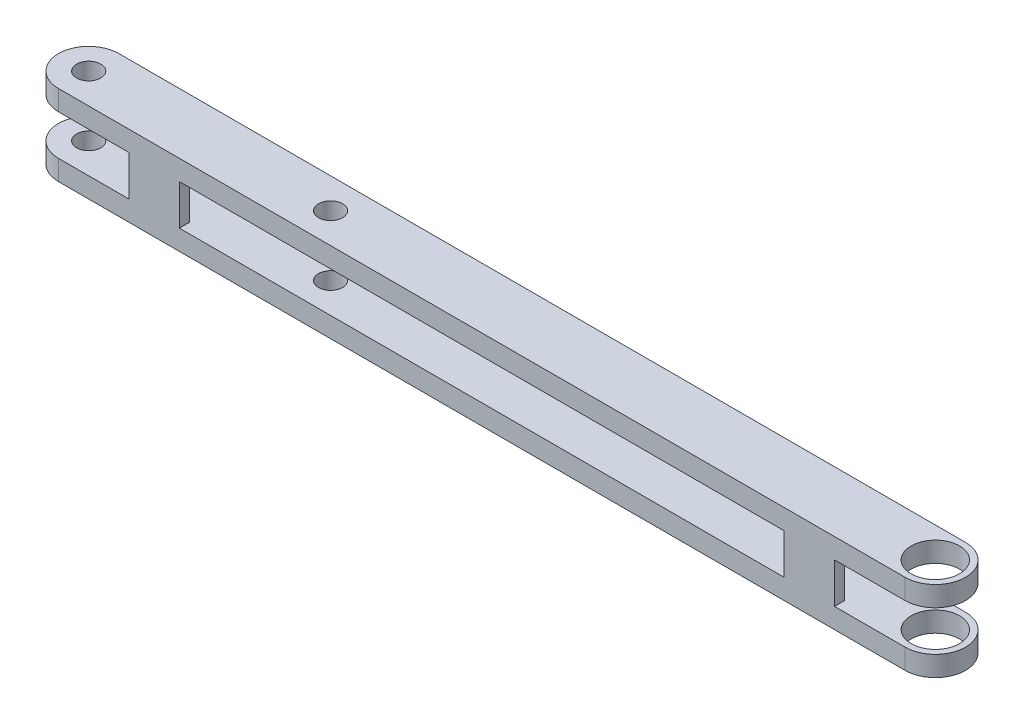
SolidWorks part; units mm, degrees
ref_plane "前视基准面" through (0, 0, 0) normal (0, 0, 1) x (1, 0, 0)
ref_plane "上视基准面" through (0, 0, 0) normal (0, 1, 0) x (1, 0, 0)
ref_plane "右视基准面" through (0, 0, 0) normal (1, 0, 0) x (0, 0, -1)
sketch "草图1" plane through (0, 0, 0) normal (0, 1, 0) x (1, 0, 0)
  line L0 (-105, 0) -> (105, 0) construction
  line L1 (-105, 7.5) -> (105, 7.5)
  line L2 (-105, -7.5) -> (105, -7.5)
  arc A0 (-105, 7.5) -> (-105, -7.5) centre (-105, 0) ccw
  arc A1 (105, -7.5) -> (105, 7.5) centre (105, 0) ccw
  point P3 (0, 0)
  dimension "D1" = 210
  dimension "D2" = 15
extrude "凸台-拉伸1" add sketch "草图1" along normal blind 20
sketch "草图2" plane through (0, 0, -7.5) normal (0, 0, -1) x (-1, 0, 0)
  line L0 (0, 0) -> (0, 10) construction
  line L1 (75, 5) -> (-75, 5)
  line L2 (75, 5) -> (75, 15)
  line L3 (75, 15) -> (-75, 15)
  line L4 (-75, 5) -> (-75, 15)
  line L5 (75, 5) -> (-75, 15) construction
  line L6 (75, 15) -> (-75, 5) construction
  line L7 (-105, 0) -> (105, 0) construction
  point P0 (0, 10)
  dimension "D1" = 10
  dimension "D2" = 10
  dimension "D3" = 150
extrude "切除-拉伸3" cut sketch "草图2" against normal through all
sketch "草图3" plane through (0, 0, -7.5) normal (0, 0, -1) x (-1, 0, 0)
  line L0 (-75, 5) -> (75, 5) construction
  line L1 (112.5, 15) -> (87.5, 15)
  line L2 (112.5, 15) -> (112.5, 5)
  line L3 (112.5, 5) -> (87.5, 5)
  line L4 (87.5, 15) -> (87.5, 5)
  line L5 (75, 15) -> (-75, 15) construction
  line L6 (112.5, 0) -> (112.5, 20) construction
  line L7 (0, 0) -> (0, 43.872) construction
  line L8 (-105, 0) -> (105, 0) construction
  line L9 (-87.5, 15) -> (-87.5, 5)
  line L10 (-112.5, 5) -> (-87.5, 5)
  line L11 (-112.5, 15) -> (-112.5, 5)
  line L12 (-112.5, 15) -> (-87.5, 15)
  dimension "D1" = 25
extrude "切除-拉伸4" cut sketch "草图3" against normal through all
sketch "草图4" plane through (-87.5, 0, 0) normal (-1, 0, 0) x (0, 0, 1)
  line L0 (7.5, 5) -> (-7.5, 5) construction
  line L1 (5, 15) -> (-5, 15)
  line L2 (5, 15) -> (5, 5)
  line L3 (5, 5) -> (-5, 5)
  line L4 (-5, 15) -> (-5, 5)
  line L5 (5, 15) -> (-5, 5) construction
  line L6 (5, 5) -> (-5, 15) construction
  line L7 (0, 0) -> (0, 10) construction
  line L8 (7.5, 15) -> (-7.5, 15) construction
  point P0 (0, 10)
  dimension "D1" = 10
extrude "切除-拉伸5" cut sketch "草图4" against normal through all
sketch "草图5" plane through (0, 20, 0) normal (0, 1, 0) x (1, 0, 0)
  line L0 (-105, 0) -> (0, 0) construction
  line L1 (0, 0) -> (105, 0) construction
  circle A0 centre (-105, 0) radius 3
  circle A1 centre (105, 0) radius 6
  dimension "D1" = 6
  dimension "D2" = 12
  dimension "D3" = 105
  dimension "D4" = 105
extrude "切除-拉伸6" cut sketch "草图5" against normal through all
sketch "草图6" plane through (0, 20, 0) normal (0, 1, 0) x (1, 0, 0)
  line L0 (-45, 0) -> (0, 0) construction
  circle A0 centre (-45, 0) radius 3
  circle A1 centre (-105, 0) radius 4 construction
  dimension "D2" = 6
  dimension "D1" = 60
extrude "切除-拉伸7" cut sketch "草图6" against normal through all
